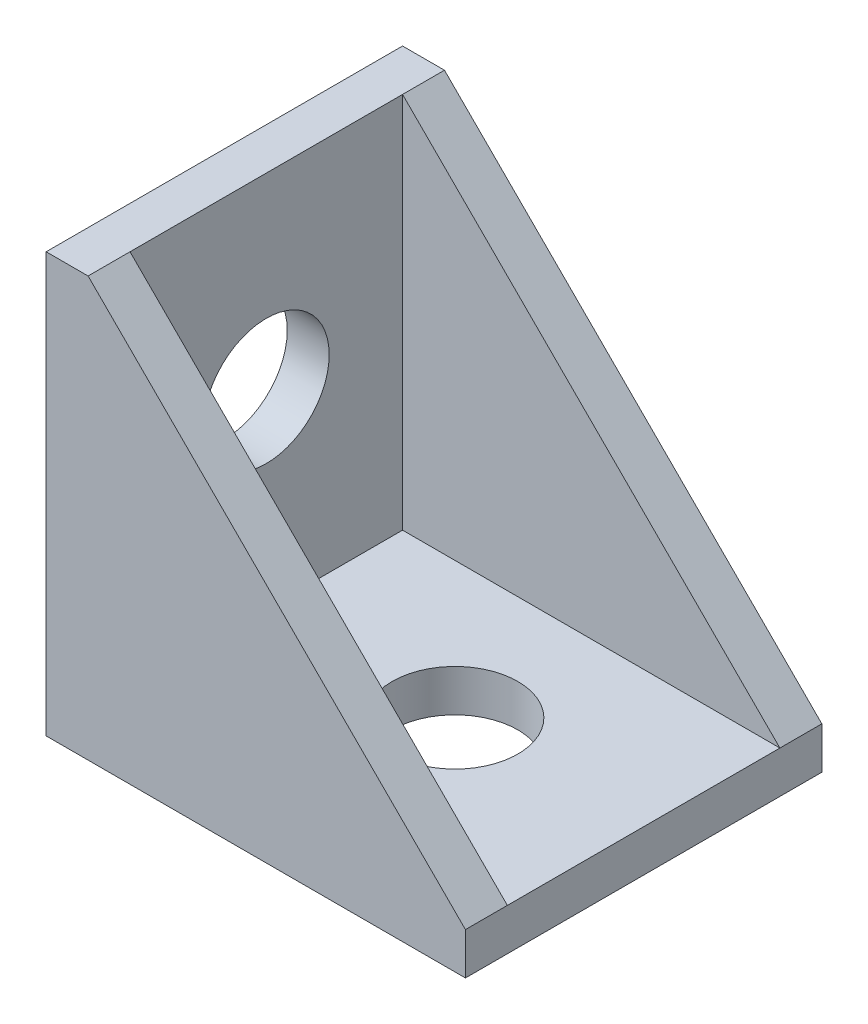
SolidWorks part; units mm, degrees
material "3.0205 (EN-AW 1200)"
ref_plane "Plano frontal" through (0, 0, 0) normal (0, 0, 1) x (1, 0, 0)
ref_plane "Plano superior" through (0, 0, 0) normal (0, 1, 0) x (1, 0, 0)
ref_plane "Plano direito" through (0, 0, 0) normal (1, 0, 0) x (0, 0, -1)
sketch "Esboço1" plane through (0, 0, 0) normal (0, 0, 1) x (1, 0, 0)
  line L0 (0, 0) -> (0, 20)
  line L1 (0, 20) -> (2, 20)
  line L2 (2, 20) -> (20, 2)
  line L3 (20, 2) -> (20, 0)
  line L4 (20, 0) -> (0, 0)
  dimension "D1" = 2
  dimension "D2" = 20
extrude "Ressalto-extrusão1" add sketch "Esboço1" along normal blind 17
sketch "Esboço2" plane through (0, 20, 0) normal (0, 1, 0) x (1, 0, 0)
  line L0 (2, -17) -> (2, 0) construction
  line L1 (2, -2) -> (20, -2)
  line L2 (2, -2) -> (2, -15)
  line L3 (2, -15) -> (20, -15)
  line L4 (20, -2) -> (20, -15)
  line L5 (20, -17) -> (20, 0) construction
  line L6 (0, -17) -> (0, 0) construction
  line L7 (20, 0) -> (2, 0) construction
  point P8 (2, -8.5)
  point P13 (0, -8.5)
  dimension "D1" = 2
extrude "Corte-extrusão1" cut sketch "Esboço2" against normal offset from surface (18 mm away) 2 up to face at (10, 0, 8.5)
sketch "Esboço3" plane through (2, 0, 0) normal (1, 0, 0) x (0, 0, -1)
  line L0 (-2, 20) -> (-15, 20) construction
  line L1 (-2, 2) -> (-2, 20) construction
  circle A0 centre (-8.5, 11) radius 3
  point P5 (-8.5, 20)
  point P9 (-2, 11)
  dimension "D1" = 6
extrude "Corte-extrusão2" cut sketch "Esboço3" against normal blind 2
sketch "Esboço4" plane through (0, 2, 0) normal (0, 1, 0) x (1, 0, 0)
  line L2 (2, -2) -> (20, -2) construction
  line L3 (20, -2) -> (20, -15) construction
  circle A0 centre (11, -8.5) radius 3
  point P8 (11, -2)
  point P9 (20, -8.5)
  dimension "D1" = 6
extrude "Corte-extrusão3" cut sketch "Esboço4" against normal through all
